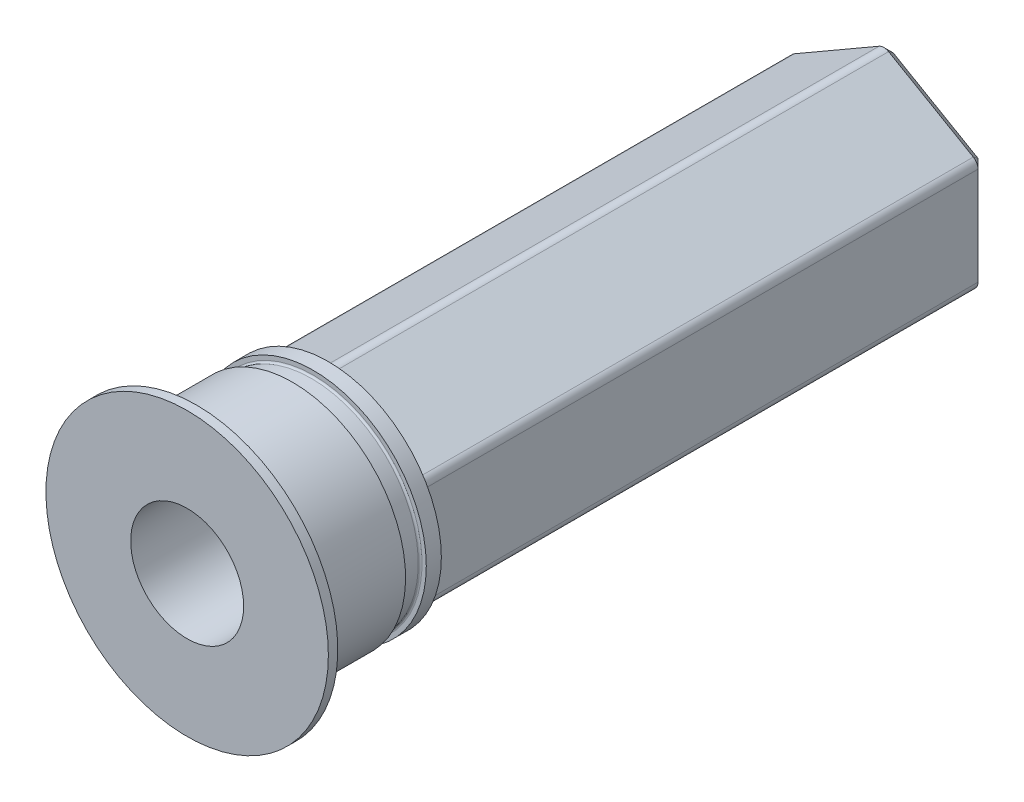
SolidWorks part; units mm, degrees
material "Alloy Steel"
ref_plane "Front" through (0, 0, 0) normal (0, 0, 1) x (1, 0, 0)
ref_plane "Top" through (0, 0, 0) normal (0, 1, 0) x (1, 0, 0)
ref_plane "Right" through (0, 0, 0) normal (1, 0, 0) x (0, 0, -1)
sketch "Sketch1" plane through (0, 0, 0) normal (0, 0, 1) x (1, 0, 0)
  circle A0 centre (0, 0) radius 3
  circle A1 centre (0, 0) radius 10.5
  dimension "D1" = 6
  dimension "D2" = 21
extrude "Extrude1" add sketch "Sketch1" against normal blind 46.5 contours A0 | A1 A0 region at (0, 0, 0) region at (-10.203, 0, 0)
extrude "Cut-Extrude1" cut sketch "Sketch1<3>" against normal through all contours A0 region at (0, 0, 0)
sketch "Sketch1<3>" plane through (0, 0, 0) normal (0, 0, 1) x (1, 0, 0) same geometry as "Sketch1"
sketch "Sketch4" plane through (0, 0, 0) normal (0, 0, 1) x (1, 0, 0)
  line L0 (-10.245, 2.3) -> (10.245, 2.3)
  arc A0 (10.245, 2.3) -> (-10.245, 2.3) centre (0, 0) ccw
  circle A1 centre (0, 0) radius 10.5 construction
  dimension "D1" = 2.3
extrude "Cut-Extrude4" cut sketch "Sketch4" against normal blind 8.5
sketch "Sketch6" plane through (0, 0, -46.5) normal (0, 0, -1) x (1, 0, 0)
  circle A0 centre (0, 0) radius 6
  circle A1 centre (0, 0) radius 10.5
  circle A2 centre (0, 0) radius 10.5 construction
  dimension "D1" = 12
extrude "Cut-Extrude6" cut sketch "Sketch6" against normal offset from surface (37 mm away) 1 up to face at (0, 4.525, -8.5)
sketch "Sketch7" plane through (0, 0, -9.5) normal (0, 0, -1) x (1, 0, 0)
  circle A0 centre (0, 0) radius 10.5
  circle A1 centre (0, 0) radius 7.5
  circle A3 centre (0, 0) radius 10.5 construction
  dimension "D1" = 15
extrude "Cut-Extrude7" cut sketch "Sketch7" against normal blind 1
hole_wizard "M4x0.7 Tapped Hole1" positions "3DSketch1" profile "Sketch10" tap size "M4x0.7" standard "Ansi Metric" end condition through all
sketch3d "3DSketch1"
  line L9 (3, 0, 0) -> (3, 0, -8.5) construction
  line L13 (-3, 0, 0) -> (-3, 0, -8.5) construction
  line L18 (3, 0, 0) -> (10.5, 0, 0) construction
  line L20 (-3, 0, 0) -> (-10.5, 0, 0) construction
  line L25 (6.25, 0, 0) -> (6.25, 0, -8.5) construction
  line L26 (3, 0, -8.5) -> (10.5, 0, -8.5) construction
  line L27 (-3, 0, -8.5) -> (-10.5, 0, -8.5) construction
  line L30 (-6.25, 0, 0) -> (-6.25, 0, -8.5) construction
  arc A1 (-1.9261, 2.3, 0) -> (1.9261, 2.3, 0) centre (0, 0, 0) ccw construction
  arc A2 (-10.245, 2.3, 0) -> (10.245, 2.3, 0) centre (0, 0, 0) ccw construction
  point P0 (6.25, 2.3, -4.25)
  point P2 (-6.25, 2.3, -4.25)
  point P33 (0, 0, 3)
  point P54 (0, 0, 10.5)
  point P93 (6.25, 0, -4.25)
  point P118 (-6.25, 0, -4.25)
  dimension "D1" = 6.25
  dimension "D2" = 6.25
sketch "Sketch10" plane through (6.25, 2.3, -4.25) normal (1, 0, 0) x (0, 0, 1)
  line L0 (0, 0) -> (0, 12.8)
  line L1 (0, 12.8) -> (1.5, 12.8)
  line L2 (1.5, 12.8) -> (1.5, 0)
  line L5 (1.5, 0) -> (0, 0)
  line L11 (0, -6.35) -> (0, 107.95) construction
  dimension "Thru Tap Drill Dia." = 3
  dimension "Thru Tap Drill Depth" = 12.8
cosmetic thread "Hole Thread3"
cosmetic thread "Hole Thread4"
sketch "Sketch8" plane through (0, 0, -46.5) normal (0, 0, -1) x (1, 0, 0)
  line L0 (0, 0) -> (0, 16.2426) construction
  line L1 (0, 5.7735) -> (-5, 2.8868)
  line L2 (-5, 2.8868) -> (-5, -2.8868)
  line L3 (-5, -2.8868) -> (0, -5.7735)
  line L4 (0, -5.7735) -> (5, -2.8868)
  line L5 (5, -2.8868) -> (5, 2.8868)
  line L6 (5, 2.8868) -> (0, 5.7735)
  circle A0 centre (0, 0) radius 5 construction
  dimension "D1" = 10
extrude "Cut-Extrude8" cut sketch "Sketch8" against normal offset from surface (30 mm away) 7 flip side to cut up to face at (6, 0, -9.5)
fillet "Fillet1" radius 0.5 6 edges at (-5, -2.8868, -31.5) (-5, 2.8868, -31.5) (0, 5.7735, -31.5) (5, 2.8868, -31.5) (5, -2.8868, -31.5) (0, -5.7735, -31.5)
chamfer "Chamfer1" distance 0.5 angle 45 12 edges at (-5, 0, -46.5) (-2.5, 4.3301, -46.5) (2.5, 4.3301, -46.5) (5, 0, -46.5) (2.5, -4.3301, -46.5) (4.933, 2.8481, -46.5) (0, 5.6962, -46.5) (4.933, -2.8481, -46.5) (-4.933, 2.8481, -46.5) (0, -5.6962, -46.5) (-4.933, -2.8481, -46.5) (-2.5, -4.3301, -46.5)
ref_plane "Plane1" through (0, 0, 19.3701) normal (-1, 0, 0) x (0, 1, 0)
sketch "Sketch12" plane through (0, 0, 19.3701) normal (-1, 0, 0) x (0, 1, 0)
  line L0 (5.775, 33.9701) -> (7.275, 33.9701)
  line L1 (7.275, 33.9701) -> (7.275, 35.0701)
  line L2 (7.275, 35.0701) -> (5.775, 35.0701)
  line L3 (5.675, 34.9701) -> (5.675, 34.0701)
  line L4 (0, -49.9891) -> (0, 54.8742) construction
  line L5 (7.5, 28.8701) -> (-7.5, 28.8701) construction
  line L8 (3, 65.8701) -> (-3, 65.8701) construction
  arc A0 (5.675, 34.0701) -> (5.775, 33.9701) centre (5.775, 34.0701) ccw
  arc A1 (5.675, 34.9701) -> (5.775, 35.0701) centre (5.775, 34.9701) cw
  point P14 (0, 65.8701)
  dimension "D1" = 0.1
  dimension "D2" = 0.1
  dimension "D3" = 5.1
  dimension "D4" = 5.675
  dimension "D5" = 1.1
  dimension "D6" = 1.5
revolve "Groove for ANSI B27.7 - 3AM1-12, Basic External Retaining Ring1" cut sketch "Sketch12"
fillet "Fillet2" radius 0.3 2 edges at (6, 0, -9.5) (0, -7.5, -8.5)
chamfer "Chamfer2" distance 1 angle 45 2 edges at (0, -10.5, -8.5) (0, -10.5, 0)
sketch "Sketch13" plane through (0, 0, 0) normal (0, 0, 1) x (1, 0, 0)
  circle A0 centre (0, 0) radius 14.5411
extrude "Cut-Extrude9" cut sketch "Sketch13" against normal blind 9
